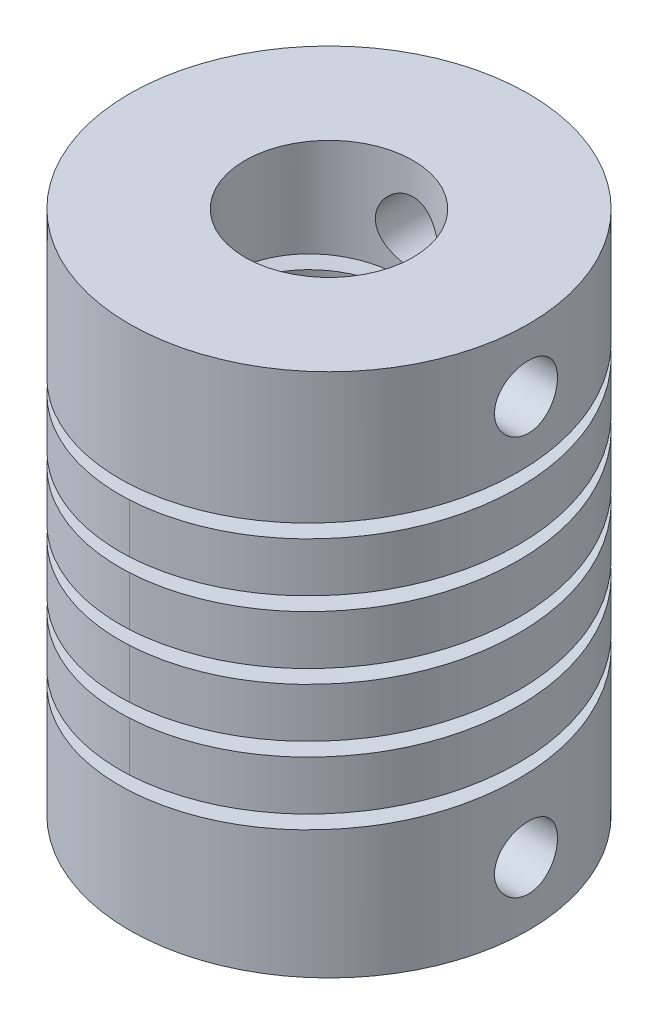
SolidWorks part; units mm, degrees
ref_plane "Přední rovina" through (0, 0, 0) normal (0, 0, 1) x (1, 0, 0)
ref_plane "Horní rovina" through (0, 0, 0) normal (0, 1, 0) x (1, 0, 0)
ref_plane "Pravá rovina" through (0, 0, 0) normal (1, 0, 0) x (0, 0, -1)
sketch "Skica1" plane through (0, 0, 0) normal (0, 1, 0) x (1, 0, 0)
  circle A0 centre (0, 0) radius 2.5
  circle A1 centre (0, 0) radius 9.5
  dimension "D1" = 5
  dimension "D2" = 19
extrude "Přidat vysunutím1" add sketch "Skica1" along normal blind 25
sketch "Skica2" plane through (0, 25, 0) normal (0, 1, 0) x (1, 0, 0)
  circle A0 centre (0, 0) radius 4
  dimension "D1" = 8
extrude "Odebrat vysunutím1" cut sketch "Skica2" against normal blind 12.5
ref_plane "Rovina1" through (0, 5, 0) normal (0, -1, 0) x (-1, 0, 0)
sketch "Skica3" plane through (0, 5, 0) normal (0, -1, 0) x (-1, 0, 0)
  circle A0 centre (0, 0) radius 9.5
curve "Šroubovice/spirála1" pitch 3 height 15 radius 9.5 centre (0, 5, 0) axis (0, 1, 0) start towards (0, 0, -1)
sketch "Skica4" plane through (0, 0, 0) normal (0, 0, 1) x (1, 0, 0)
  line L0 (-10.45, 5) -> (10.45, 5) construction
  line L1 (-9.5, 5) -> (-1.9434, 5)
  line L2 (-9.5, 5) -> (-9.5, 5.6516)
  line L3 (-9.5, 5.6516) -> (-1.9434, 5.6516)
  line L4 (-1.9434, 5) -> (-1.9434, 5.6516)
  spline S0 degree 3 poles (-9.5, 5) (-9.5, 5.0621) (-9.0054, 5.1877) (-6.8924, 5.375) (-3.7301, 5.5625) (0, 5.75) (3.7301, 5.9375) (6.8924, 6.125) (9.0054, 6.3125) (9.7473, 6.5) (9.0054, 6.6875) (6.8924, 6.875) (3.7301, 7.0625) (0, 7.25) (-3.7301, 7.4375) (-6.8924, 7.625) (-9.0054, 7.8125) (-9.7473, 8) (-9.0054, 8.1875) (-6.8924, 8.375) (-3.7301, 8.5625) (0, 8.75) (3.7301, 8.9375) (6.8924, 9.125) (9.0054, 9.3125) (9.7473, 9.5) (9.0054, 9.6875) (6.8924, 9.875) (3.7301, 10.0625) (0, 10.25) (-3.7301, 10.4375) (-6.8924, 10.625) (-9.0054, 10.8125) (-9.7473, 11) (-9.0054, 11.1875) (-6.8924, 11.375) (-3.7301, 11.5625) (0, 11.75) (3.7301, 11.9375) (6.8924, 12.125) (9.0054, 12.3125) (9.7473, 12.5) (9.0054, 12.6875) (6.8924, 12.875) (3.7301, 13.0625) (0, 13.25) (-3.7301, 13.4375) (-6.8924, 13.625) (-9.0054, 13.8125) (-9.7473, 14) (-9.0054, 14.1875) (-6.8924, 14.375) (-3.7301, 14.5625) (0, 14.75) (3.7301, 14.9375) (6.8924, 15.125) (9.0054, 15.3125) (9.7473, 15.5) (9.0054, 15.6875) (6.8924, 15.875) (3.7301, 16.0625) (0, 16.25) (-3.7301, 16.4375) (-6.8924, 16.625) (-9.0054, 16.8125) (-9.7473, 17) (-9.0054, 17.1875) (-6.8924, 17.375) (-3.7301, 17.5625) (0, 17.75) (3.7301, 17.9375) (6.8924, 18.125) (9.0054, 18.3125) (9.7473, 18.5) (9.0054, 18.6875) (6.8924, 18.875) (3.7301, 19.0625) (0, 19.25) (-3.7301, 19.4375) (-6.8924, 19.625) (-9.0054, 19.8123) (-9.5, 19.9379) (-9.5, 20) knots 0 0 0 0 0.0125 0.025 0.0375 0.05 0.0625 0.075 0.0875 0.1 0.1125 0.125 0.1375 0.15 0.1625 0.175 0.1875 0.2 0.2125 0.225 0.2375 0.25 0.2625 0.275 0.2875 0.3 0.3125 0.325 0.3375 0.35 0.3625 0.375 0.3875 0.4 0.4125 0.425 0.4375 0.45 0.4625 0.475 0.4875 0.5 0.5125 0.525 0.5375 0.55 0.5625 0.575 0.5875 0.6 0.6125 0.625 0.6375 0.65 0.6625 0.675 0.6875 0.7 0.7125 0.725 0.7375 0.75 0.7625 0.775 0.7875 0.8 0.8125 0.825 0.8375 0.85 0.8625 0.875 0.8875 0.9 0.9125 0.925 0.9375 0.95 0.9625 0.975 0.9875 1 1 1 1 construction
sweep "Odebrat tažením po křivce2" cut profiles "Skica4" path "Šroubovice/spirála1" align with end faces yes
sketch "Skica11" plane through (0, 0, 0) normal (0, 0, 1) x (1, 0, 0)
  line L0 (4, 25) -> (-4, 25) construction
  circle A0 centre (0, 3) radius 1.5
  circle A1 centre (0, 22) radius 1.5
  dimension "D1" = 3
  dimension "D4" = 3
  dimension "D2" = 3
  dimension "D3" = 3
extrude "Odebrat vysunutím2" cut sketch "Skica11" against normal blind 12.5
sketch "Skica12" plane through (0, 0, 0) normal (1, 0, 0) x (0, 0, -1)
  line L0 (-9.5, 0) -> (9.5, 0) construction
  line L1 (4, 25) -> (-4, 25) construction
  circle A0 centre (0, 22) radius 1.5
  circle A1 centre (0, 3) radius 1.5
  dimension "D1" = 3
  dimension "D2" = 3
  dimension "D3" = 3
extrude "Odebrat vysunutím3" cut sketch "Skica12" along normal blind 12.5
